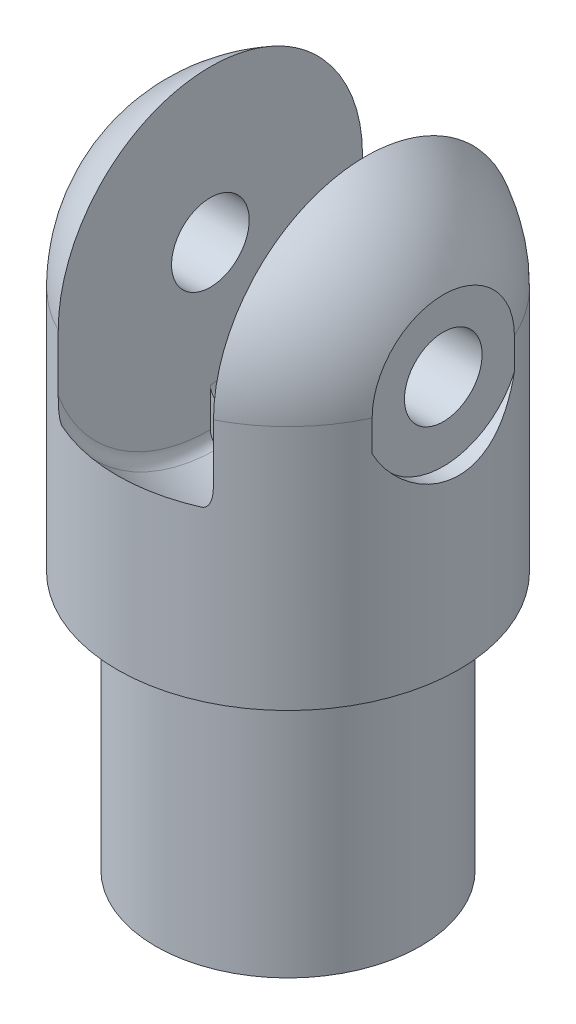
SolidWorks part; units mm, degrees
ref_plane "Front Plane" through (0, 0, 0) normal (0, 0, 1) x (1, 0, 0)
ref_plane "Top Plane" through (0, 0, 0) normal (0, 1, 0) x (1, 0, 0)
ref_plane "Right Plane" through (0, 0, 0) normal (1, 0, 0) x (0, 0, -1)
sketch "Sketch1" plane through (0, 0, 0) normal (0, 1, 0) x (1, 0, 0)
  circle A0 centre (0, 0) radius 12.9921
  dimension "D1" = 25.9842
extrude "Boss-Extrude1" add sketch "Sketch1" along normal blind 25.4 contours A0
sketch "Sketch2" plane through (0, 0, 0) normal (1, 0, 0) x (0, 0, -1)
  line L0 (-16.764, 25.4) -> (-16.764, 49.53)
  line L1 (0, 25.4) -> (-16.764, 25.4)
  line L4 (12.9921, 25.4) -> (-12.9921, 25.4) construction
  line L5 (0, 55) -> (0, -55) construction
  line L6 (0, 25.4) -> (0, 66.294)
  arc A0 (0, 66.294) -> (-16.764, 49.53) centre (0, 49.53) ccw
  dimension "D1" = 33.528
  dimension "D2" = 24.13
revolve "Revolve1" add sketch "Sketch2" angle 360 about L6
ref_plane "Plane2" through (0, 49.53, 0) normal (0, -1, 0) x (-1, 0, 0)
ref_axis "Axis1" through (0, 49.53, 23.7) along (0, 0, -1)
ref_plane "Plane3" through (0, 49.53, 0) normal (0, -1, 0) x (0, 0, -1)
ref_plane "Plane4" through (0, 0, 0) normal (-1, 0, 0) x (0, 0, -1)
sketch "Sketch3" plane through (0, 98.3075, 0) normal (-1, 0, 0) x (0, 0, -1)
  line L1 (-23.7, 48.7775) -> (13.1808, 48.7775) construction
  line L2 (0, 48.7775) -> (0, 72.9075) construction
  circle A2 centre (0, 48.7775) radius 3.81
  dimension "D1" = 7.62
extrude "Cut-Extrude1" cut sketch "Sketch3" against normal through all both and the other way through all
ref_axis "Axis2" through (16.764, 49.53, 0) along (-1, 0, 0)
sketch "Sketch10" plane through (0, 0, 0) normal (0, 0, 1) x (1, 0, 0)
  line L0 (16.764, 49.53) -> (-16.764, 49.53) construction
  line L1 (-7.62, 49.53) -> (7.62, 49.53)
  point P5 (0, 49.53)
  dimension "D1" = 15.24
  dimension "D2" = 0
sketch "Sketch11" plane through (0, 0, 0) normal (0, 0, 1) x (1, 0, 0)
  line L2 (-7.62, 49.53) -> (7.62, 49.53) construction
  line L3 (-7.62, 49.53) -> (-7.62, 66.2945)
  line L4 (7.62, 49.53) -> (7.62, 66.2945)
  line L5 (-7.62, 49.53) -> (7.62, 49.53)
  arc A0 (7.62, 66.2945) -> (-7.62, 66.2945) centre (0, 49.53) ccw
  arc A1 (16.3253, 53.34) -> (-16.3253, 53.34) centre (0, 49.53) ccw construction
  dimension "D1" = 18.415
revolve "Cut-Revolve10" cut sketch "Sketch11" angle 90 about axis through (16.764, 49.53, 0) along (-1, 0, 0) other way angle 180
sketch "Sketch13" plane through (0, 0, 0) normal (0, 0, 1) x (1, 0, 0)
  line L0 (-7.62, 53.34) -> (7.62, 53.34)
  line L1 (-7.62, 49.53) -> (-7.62, 64.4621) construction
  line L2 (7.62, 64.4621) -> (7.62, 49.53) construction
  line L3 (-7.62, 49.53) -> (7.62, 49.53) construction
  line L4 (-7.62, 53.34) -> (-7.62, 70.1045)
  line L5 (7.62, 53.34) -> (7.62, 70.1045)
  arc A0 (7.62, 70.1045) -> (-7.62, 70.1045) centre (0, 53.34) ccw
  dimension "D1" = 3.81
  dimension "D2" = 36.83
revolve "Cut-Revolve11" cut sketch "Sketch13" angle 360 about L0
sketch "Sketch14" plane through (0, 0, 0) normal (0, 0, 1) x (1, 0, 0)
  line L0 (-7.62, 49.53) -> (7.62, 49.53) construction
  line L1 (-7.62, 49.53) -> (-7.62, 42.064)
  line L2 (7.62, 49.53) -> (7.62, 42.064)
  line L3 (-7.62, 49.53) -> (7.62, 49.53)
  arc A0 (-7.62, 42.064) -> (7.62, 42.064) centre (0, 49.53) ccw
  dimension "D1" = 21.336
extrude "Cut-Extrude4" cut sketch "Sketch14" against normal blind 32.004
fillet "Fillet1" radius 1.27 6 edges at (-7.62, 35.233, 8.7546) (-7.62, 38.0089, -6.7827) (-7.62, 42.064, -13.6688) (7.62, 42.064, -13.6688) (7.62, 38.0089, -6.7827) (7.62, 35.233, 8.7546)
ref_plane "Plane5" through (-15.24, 0, 0) normal (-1, 0, 0) x (0, 0, -1)
sketch "Sketch15" plane through (-15.24, 0, 0) normal (-1, 0, 0) x (0, 0, -1)
  circle A0 centre (0, -49.53) radius 7.62
  dimension "D1" = 15.24
extrude "Cut-Extrude5" cut sketch "Sketch15" along normal blind 10.16
mirror "Mirror1" about plane through (0, 0, 0) normal (-1, 0, 0) of "Cut-Extrude5"
